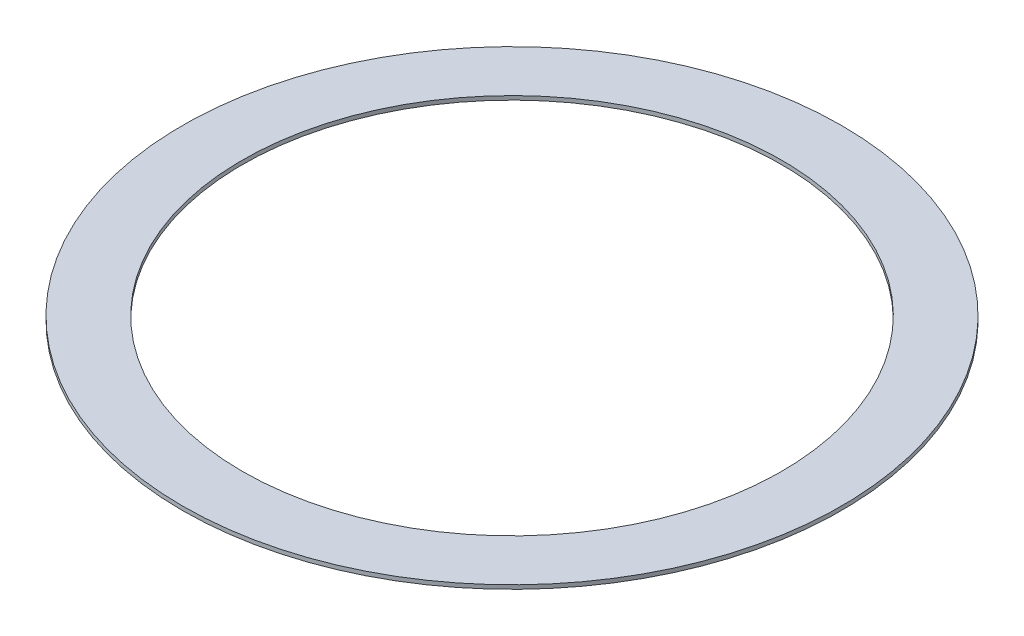
SolidWorks part; units mm, degrees
ref_plane "Front Plane" through (0, 0, 0) normal (0, 0, 1) x (1, 0, 0)
ref_plane "Top Plane" through (0, 0, 0) normal (0, 1, 0) x (1, 0, 0)
ref_plane "Right Plane" through (0, 0, 0) normal (1, 0, 0) x (0, 0, -1)
sketch "Sketch1" plane through (0, 0, 0) normal (0, 1, 0) x (1, 0, 0)
  circle A0 centre (0, 0) radius 69.85
  circle A1 centre (0, 0) radius 57.15
  dimension "D1" = 139.7
  dimension "D2" = 114.3
extrude "Boss-Extrude1" add sketch "Sketch1" along normal blind 0.8382
